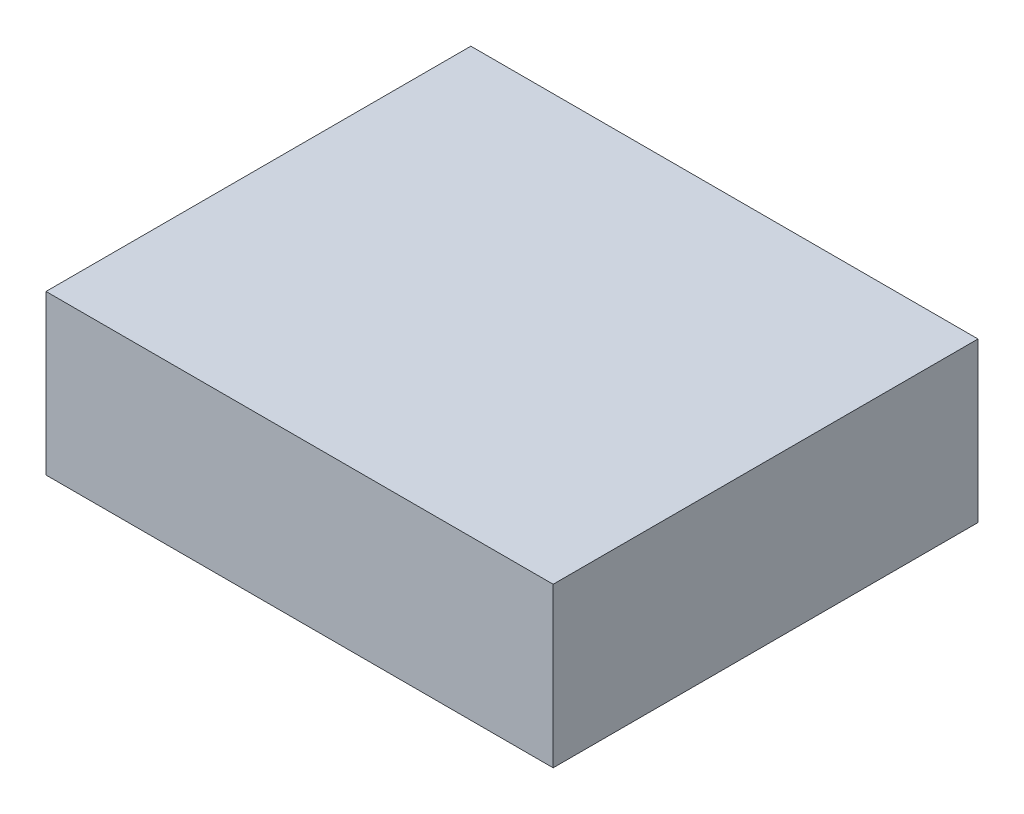
SolidWorks part; units mm, degrees
ref_plane "Front Plane" through (0, 0, 0) normal (0, 0, 1) x (1, 0, 0)
ref_plane "Top Plane" through (0, 0, 0) normal (0, 1, 0) x (1, 0, 0)
ref_plane "Right Plane" through (0, 0, 0) normal (1, 0, 0) x (0, 0, -1)
sketch "Sketch1" plane through (0, 0, 0) normal (0, 1, 0) x (1, 0, 0)
  line L1 (-12.5984, 10.5537) -> (12.5984, 10.5537)
  line L2 (-12.5984, 10.5537) -> (-12.5984, -10.5537)
  line L3 (-12.5984, -10.5537) -> (12.5984, -10.5537)
  line L4 (12.5984, 10.5537) -> (12.5984, -10.5537)
  line L5 (-12.5984, 10.5537) -> (12.5984, -10.5537) construction
  line L6 (-12.5984, -10.5537) -> (12.5984, 10.5537) construction
  point P0 (0, 0)
  dimension "D1" = 25.1968
  dimension "D2" = 21.1074
extrude "Boss-Extrude1" add sketch "Sketch1" along normal blind 7.8994
